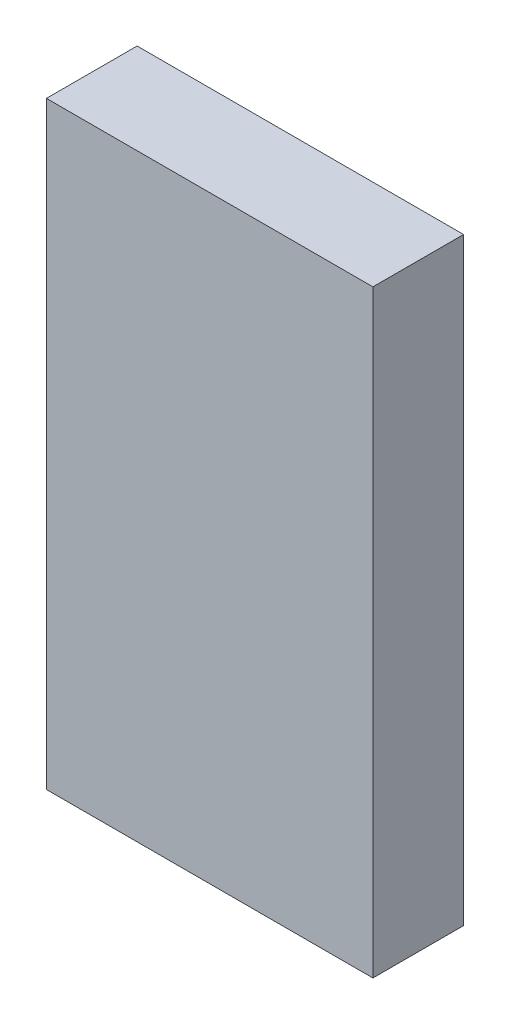
SolidWorks part; units mm, degrees
ref_plane "前视基准面" through (0, 0, 0) normal (0, 0, 1) x (1, 0, 0)
ref_plane "上视基准面" through (0, 0, 0) normal (0, 1, 0) x (1, 0, 0)
ref_plane "右视基准面" through (0, 0, 0) normal (1, 0, 0) x (0, 0, -1)
ref_plane "基准面1" through (0, 0, 12) normal (0, 0, 1) x (1, 0, 0)
sketch "草图1" plane through (0, 0, 12) normal (0, 0, 1) x (1, 0, 0)
  line L0 (19, 66) -> (19, 0)
  line L1 (19, 0) -> (55, 0)
  line L2 (55, 0) -> (55, 66)
  line L3 (55, 66) -> (19, 66)
  dimension "D1" = 66
  dimension "D2" = 36
extrude "凸台-拉伸1" add sketch "草图1" against normal blind 10
